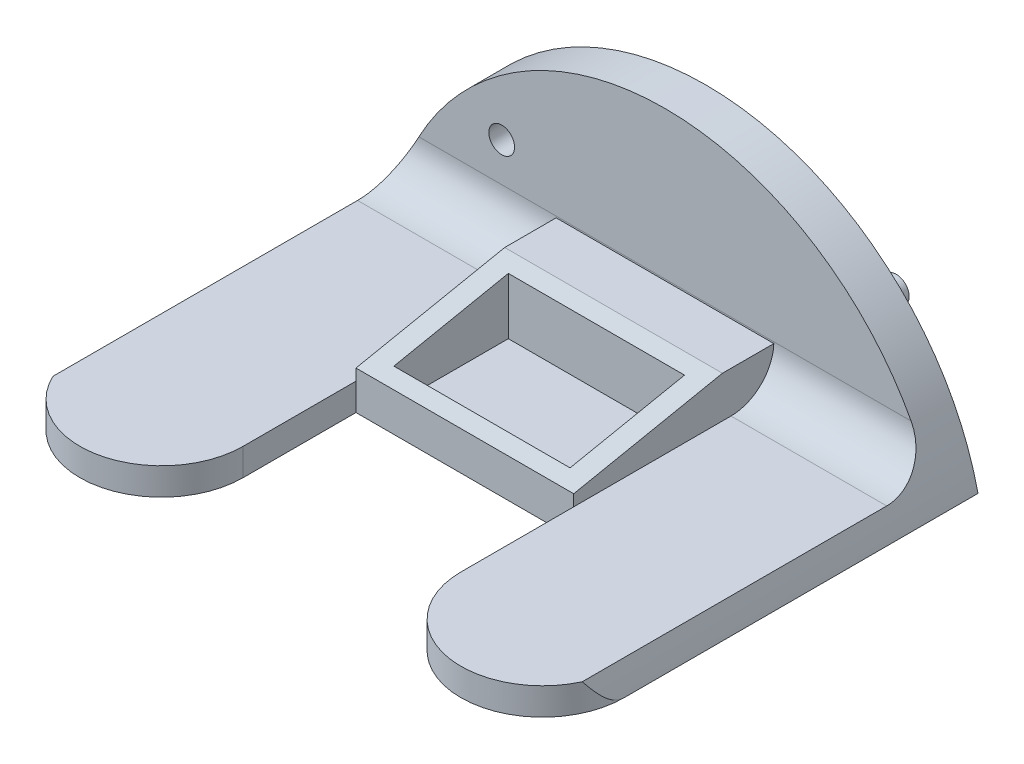
SolidWorks part; units mm, degrees
ref_plane "Front Plane" through (0, 0, 0) normal (0, 0, 1) x (1, 0, 0)
ref_plane "Top Plane" through (0, 0, 0) normal (0, 1, 0) x (1, 0, 0)
ref_plane "Right Plane" through (0, 0, 0) normal (1, 0, 0) x (0, 0, -1)
sketch "Sketch2" plane through (0, 0, 0) normal (1, 0, 0) x (0, 0, -1)
  line L0 (-50.8, 0) -> (0, 0)
  line L1 (0, 0) -> (0, 25.4)
  line L3 (-4.7625, 25.4) -> (-4.7625, 3.175)
  line L4 (-4.7625, 3.175) -> (-50.8, 3.175)
  line L6 (-4.7625, 25.4) -> (0, 25.4)
  line L7 (-50.8, 3.175) -> (-50.8, 0)
  dimension "D1" = 4.7625
  dimension "D2" = 3.175
  dimension "D3" = 25.4
  dimension "D4" = 50.8
extrude "Boss-Extrude1" add sketch "Sketch2" along normal blind 63.5
sketch "Sketch3" plane through (0, 0, 0) normal (0, 0, -1) x (-1, 0, 0)
  line L0 (-50.8, 12.7) -> (-12.7, 12.7) construction
  line L1 (-63.5, 0) -> (0, 0) construction
  circle A0 centre (-50.8, 12.7) radius 1.5
  circle A1 centre (-12.7, 12.7) radius 1.5
  point P4 (-31.75, 12.7)
  point P7 (-31.75, 0)
  dimension "D3" = 3
  dimension "D1" = 12.7
  dimension "D2" = 38.1
extrude "Cut-Extrude1" cut sketch "Sketch3" against normal through all contours A1 | A1 region at (12.7, 12.7, 0)
extrude "Boss-Extrude2" add sketch "Sketch3<3>" along normal blind 3.175 contours A0 region at (50.8, 12.7, 0)
sketch "Sketch3<3>" plane through (0, 0, 0) normal (0, 0, -1) x (-1, 0, 0) same geometry as "Sketch3"
sketch "Sketch4" plane through (0, 0, 0) normal (0, 0, -1) x (-1, 0, 0)
  line L0 (-63.5, 0) -> (-63.5, 25.4)
  line L3 (-63.5, 25.4) -> (0, 25.4)
  line L4 (0, 25.4) -> (0, 0)
  line L5 (0, 0) -> (-63.5, 0)
  arc A0 (0, 0) -> (-63.5, 0) centre (-31.75, -7.1438) ccw
  line M7 (0, 0) -> (0, 25.4)
  line M9 (-63.5, 25.4) -> (-63.5, 0)
extrude "Cut-Extrude2" cut sketch "Sketch4" against normal through all contours M9 | L3 L0 | M7 | L3 L4 region at (56.285, 18.8467, 0) region at (7.215, 18.8467, 0)
sketch "Sketch5" plane through (0, 3.175, 0) normal (0, 1, 0) x (1, 0, 0)
  line L0 (0, -4.7625) -> (63.5, -4.7625)
  line L1 (63.5, -50.8) -> (63.5, 0) construction
  line L2 (0, -50.8) -> (0, 0) construction
  line L3 (0.8855, -4.7625) -> (62.6145, -4.7625) construction
  line L4 (0, -4.7625) -> (0, -50.8)
  line L5 (0, -50.8) -> (63.5, -50.8)
  line L6 (63.5, -50.8) -> (63.5, -4.7625)
  line L7 (0, -4.7625) -> (0, -41.275)
  line L8 (19.05, -41.275) -> (19.05, -4.7625)
  line L9 (63.5, -4.7625) -> (63.5, -41.275)
  line L10 (44.45, -41.275) -> (44.45, -4.7625)
  arc A1 (0, -41.275) -> (19.05, -41.275) centre (9.525, -41.275) ccw
  arc A2 (63.5, -41.275) -> (44.45, -41.275) centre (53.975, -41.275) cw
  line M8 (0.8855, -4.7625) -> (0.8855, -50.8)
  line M9 (0.8855, -50.8) -> (62.6145, -50.8)
  line M10 (62.6145, -50.8) -> (62.6145, -4.7625)
  dimension "D1" = 19.05
extrude "Cut-Extrude3" cut sketch "Sketch5" against normal blind 3.175 contours L5 A2 L10 L0 L8 A1 | A1 M8 M9 | A1 L4 L5 M8 | A2 M10 M9 | L6 A2 L5 M10 region at (0.4083, 3.175, 47.3224) region at (31.75, 3.175, 28.4545) region at (2.9015, 3.175, 49.2801) region at (60.5985, 3.175, 49.2801) region at (63.0917, 3.175, 47.3224)
sketch "Sketch6" plane through (0, 0, 0) normal (0, -1, 0) x (1, 0, 0)
  line L0 (19.05, 41.275) -> (19.05, 4.7625) construction
  line L1 (19.05, 28.1125) -> (44.45, 28.1125)
  line L2 (19.05, 28.1125) -> (19.05, 4.7625)
  line L3 (19.05, 4.7625) -> (44.45, 4.7625)
  line L4 (44.45, 28.1125) -> (44.45, 4.7625)
  line L5 (19.05, 10.7625) -> (44.45, 10.7625)
  line L6 (21.475, 12.7625) -> (42.025, 12.7625)
  line L7 (21.475, 12.7625) -> (21.475, 26.1125)
  line L8 (21.475, 26.1125) -> (42.025, 26.1125)
  line L9 (42.025, 12.7625) -> (42.025, 26.1125)
  point P11 (31.75, 26.1125)
  point P12 (31.75, 28.1125)
  line M14 (44.45, 41.275) -> (44.45, 4.7625)
  line M15 (44.45, 4.7625) -> (19.05, 4.7625)
  line M16 (19.05, 4.7625) -> (19.05, 41.275)
  dimension "D1" = 13.35
  dimension "D2" = 20.55
  dimension "D3" = 8
  dimension "D4" = 2
  dimension "D5" = 2
extrude "Boss-Extrude3" add sketch "Sketch6" against normal blind 1 contours L6 L9 L8 L7 | L1 L9 L6 L7 L8 M16 M15 M14 region at (31.75, 0, 27.8049) region at (31.75, 0, 19.4375)
extrude "Boss-Extrude4" add sketch "Sketch6<3>" against normal blind 7 from surface contours L1 L9 L6 L7 L8 M16 M15 M14 | L5 L4 M16 M15 region at (31.75, 0, 27.8049) region at (31.75, 0, 7.7625) starting at face at (31.75, 1, 19.4375)
sketch "Sketch6<3>" plane through (0, 0, 0) normal (0, -1, 0) x (1, 0, 0) same geometry as "Sketch6"
sketch "Sketch7" plane through (19.05, 0, 0) normal (-1, 0, 0) x (0, 0, 1)
  line L0 (10.7625, 8) -> (28.1125, 8)
  line L1 (28.1125, 8) -> (28.1125, 4.5)
  line L2 (28.1125, 4.5) -> (10.7625, 8)
  line L3 (41.275, 0) -> (0, 0) construction
  line L4 (28.1125, 8) -> (28.1125, 3.175) construction
  line L5 (4.7625, 8) -> (28.1125, 8) construction
  point P2 (0, 0)
  point P8 (0, 0)
  point P9 (7.425, 11)
  point P11 (0, 0)
  point P12 (0, 0)
  point P13 (24.775, 11)
  point P18 (0, 0)
  point P19 (0, 0)
  point P20 (0, 0)
  point P21 (0, 0)
  dimension "D1" = 4.5
  dimension "D2" = 2
extrude "Cut-Extrude4" cut sketch "Sketch7" against normal through all
extrude "Boss-Extrude5" add sketch "Sketch6<4>" along direction (0, -1, 0) on the side against the normal up to surface (3.175 mm away) contours L5 L4 M16 M15 region at (31.75, 0, 7.7625) up to face at (12.1064, 3.175, 26.2988)
sketch "Sketch6<4>" plane through (0, 0, 0) normal (0, -1, 0) x (1, 0, 0) same geometry as "Sketch6"
fillet "Fillet2" radius 5 1 edges at (9.9677, 3.175, 4.7625)
